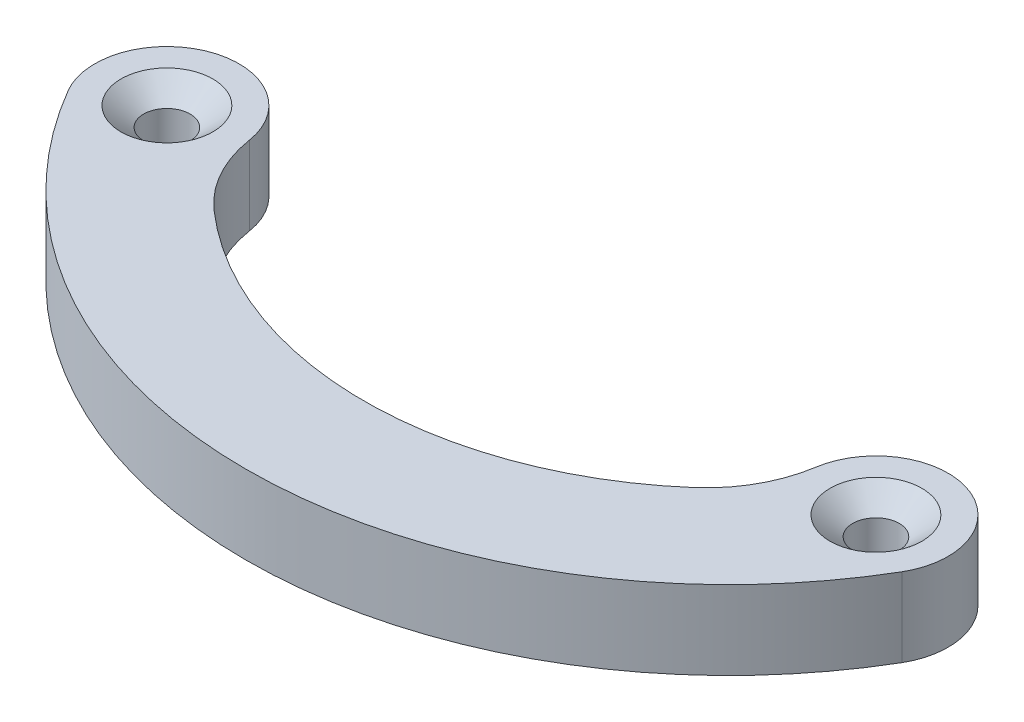
SolidWorks part; units mm, degrees
ref_plane "Front Plane" through (0, 0, 0) normal (0, 0, 1) x (1, 0, 0)
ref_plane "Top Plane" through (0, 0, 0) normal (0, 1, 0) x (1, 0, 0)
ref_plane "Right Plane" through (0, 0, 0) normal (1, 0, 0) x (0, 0, -1)
sketch "Sketch1" plane through (0, 0, 0) normal (0, 1, 0) x (1, 0, 0)
  line L0 (0, -35.306) -> (0, -46.736)
  arc A0 (0, -32.766) -> (24.8155, -21.3963) centre (0, 0) ccw construction
  arc A1 (40.3444, -23.592) -> (27.4132, -18.9891) centre (34.3147, -20.066) ccw
  arc A2 (0, -46.736) -> (40.3444, -23.592) centre (0, 0) ccw
  arc A3 (0, -35.306) -> (23.2162, -26.5993) centre (0, 0) ccw
  arc A4 (27.4132, -18.9891) -> (23.2162, -26.5993) centre (14.865, -17.0312) cw
  dimension "D1" = 65.532
  dimension "D2" = 2.54
  dimension "D3" = 13.97
  dimension "D5" = 12.7
  dimension "D4" = 15.24
extrude "Boss-Extrude1" add sketch "Sketch1" along normal blind 7.62
hole_wizard "CSK for #8 Flat Head Machine Screw (100)1" positions "Sketch2" profile "Sketch3" countersink size "#8" standard "ANSI Inch" end condition through all
sketch "Sketch2" plane through (0, 7.62, 0) normal (0, 1, 0) x (1, 0, 0)
  point P0 (34.3147, -20.066)
sketch "Sketch3" plane through (34.3147, 7.62, 20.066) normal (1, 0, 0) x (0, 0, 1)
  line L0 (0, 0) -> (0, 7.62)
  line L1 (0, 7.62) -> (2.2479, 7.62)
  line L2 (2.2479, 7.62) -> (2.2479, 1.8436)
  line L3 (2.2479, 1.8436) -> (4.445, 0)
  line L5 (4.445, 0) -> (0, 0)
  line L6 (-2.2479, 1.8436) -> (-4.445, 0) construction
  line L11 (0, -6.35) -> (0, 107.95) construction
  dimension "Thru Hole Dia." = 4.4958
  dimension "Thru Hole Depth" = 7.62
  dimension "Near C'Sink Dia." = 8.89
  dimension "Near C'Sink Angle" = 100
mirror "Mirror1" about plane through (0, 0, 0) normal (1, 0, 0) of bodies 106
